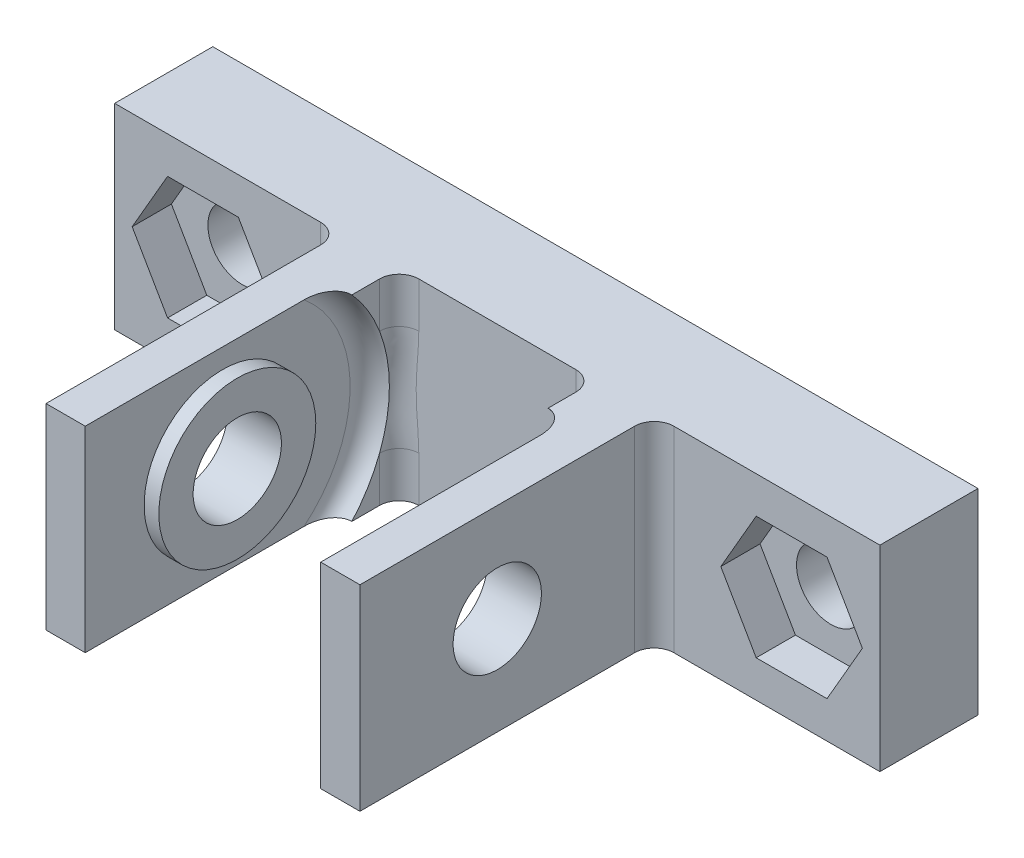
SolidWorks part; units mm, degrees
ref_plane "Front Plane" through (0, 0, 0) normal (0, 0, 1) x (1, 0, 0)
ref_plane "Top Plane" through (0, 0, 0) normal (0, 1, 0) x (1, 0, 0)
ref_plane "Right Plane" through (0, 0, 0) normal (1, 0, 0) x (0, 0, -1)
sketch "Sketch1" plane through (0, 0, 0) normal (0, 1, 0) x (1, 0, 0)
  line L0 (0, 0) -> (0, -20.0709) construction
  line L1 (-8, 0) -> (8, 0)
  line L2 (8, 0) -> (8, -20)
  line L3 (8, -20) -> (5, -20)
  line L4 (5, -20) -> (5, -5)
  line L5 (5, -5) -> (-5, -5)
  line L6 (-5, -20) -> (-5, -5)
  line L7 (-8, -20) -> (-5, -20)
  line L8 (-8, 0) -> (-8, -20)
  line L9 (5, -20) -> (5, -5)
  point P9 (0, -5)
  dimension "D1" = 5
  dimension "D2" = 3
  dimension "D3" = 15
  dimension "D4" = 5
extrude "Boss-Extrude1" add sketch "Sketch1" along normal blind 10 contours L1 L0 L5 L4 L3 L2 | L0 L1 L8 L7 L6 L5 region at (5.3235, 0, 7.7941) region at (-5.3235, 0, 7.7941)
sketch "Sketch2" plane through (8, 0, 0) normal (1, 0, 0) x (0, 0, -1)
  line L0 (-20, 5) -> (0, 5) construction
  line L1 (-20, 10) -> (-20, 0) construction
  line L2 (0, 10) -> (0, 0) construction
  circle A0 centre (-13, 5) radius 2.25
  dimension "D1" = 4.5
  dimension "D2" = 13
extrude "Cut-Extrude1" cut sketch "Sketch2" against normal through all contours A0
sketch "Sketch3" plane through (0, 10, 0) normal (0, 1, 0) x (1, 0, 0)
  line L1 (-19.5, -5) -> (19.5, -5)
  line L2 (0, 0) -> (0, -5) construction
  line L3 (-19.5, 0) -> (19.5, 0)
  line L4 (19.5, -5) -> (19.5, 0)
  line L5 (-8, 0) -> (8, 0) construction
  line L7 (-19.5, -5) -> (-19.5, 0)
  line L8 (5, -5) -> (-5, -5) construction
  dimension "D1" = 19.5
extrude "Boss-Extrude2" add sketch "Sketch3" against normal through all
sketch "Sketch4" plane through (0, 0, 5) normal (0, 0, 1) x (1, 0, 0)
  line L0 (-19.5, 5) -> (-8, 5) construction
  line L1 (-19.5, 0) -> (-19.5, 10) construction
  line L2 (-8, 10) -> (-8, 0) construction
  line L3 (-15, 0) -> (-15, 10) construction
  line L6 (0, 0) -> (0, 10) construction
  line L7 (5, 0) -> (-5, 0) construction
  line L8 (5, 10) -> (-5, 10) construction
  line L9 (15, 0) -> (15, 10) construction
  line L10 (19.5, 5) -> (8, 5) construction
  line L11 (-15, 0) -> (-15, 10) construction
  circle A0 centre (-15, 5) radius 1.75
  circle A1 centre (15, 5) radius 1.75
  dimension "D1" = 3.5
  dimension "D2" = 15
extrude "Cut-Extrude2" cut sketch "Sketch4" against normal through all
sketch "Sketch6" plane through (-5, 0, 0) normal (1, 0, 0) x (0, 0, -1)
  line L0 (-13, 12.5) -> (-20.5, 12.5)
  line L1 (-20.5, 12.5) -> (-20.5, 5)
  line L2 (-20.5, 5) -> (-20.5, -2.5)
  line L3 (-20.5, -2.5) -> (-13, -2.5)
  arc A0 (-13, -2.5) -> (-13, 12.5) centre (-13, 5) ccw
  circle A1 centre (-13, 5) radius 2.25 construction
  dimension "D1" = 15
extrude "Cut-Extrude3" cut sketch "Sketch6" against normal blind 1
sketch "Sketch5" plane through (-6, 0, 0) normal (1, 0, 0) x (0, 0, -1)
  circle A0 centre (-13, 5) radius 4
  circle A1 centre (-13, 5) radius 2.25
  circle A2 centre (-13, 5) radius 2.25 construction
  dimension "D1" = 8
extrude "Boss-Extrude3" add sketch "Sketch5" along normal blind 0.75
mirror "Mirror1" about plane through (0, 0, 0) normal (1, 0, 0) of "Boss-Extrude3", "Cut-Extrude3"
fillet "Fillet1" radius 1 6 edges at (-6, 5, 5.5) (6, 5, 5.5) (5, 5, 5) (-5, 5, 5) (8, 5, 5) (-8, 5, 5)
sketch "Sketch7" plane through (0, 0, 5) normal (0, 0, 1) x (1, 0, 0)
  line L0 (0, 10) -> (0, 0) construction
  line L1 (16.8042, 8.125) -> (13.1958, 8.125)
  line L2 (13.1958, 8.125) -> (11.3916, 5)
  line L3 (11.3916, 5) -> (13.1958, 1.875)
  line L4 (13.1958, 1.875) -> (16.8042, 1.875)
  line L5 (16.8042, 1.875) -> (18.6084, 5)
  line L6 (18.6084, 5) -> (16.8042, 8.125)
  line L7 (4, 10) -> (-4, 10) construction
  line L8 (-18.6084, 5) -> (-16.8042, 8.125)
  line L9 (-16.8042, 1.875) -> (-18.6084, 5)
  line L10 (-13.1958, 1.875) -> (-16.8042, 1.875)
  line L11 (-11.3916, 5) -> (-13.1958, 1.875)
  line L12 (-13.1958, 8.125) -> (-11.3916, 5)
  line L13 (-16.8042, 8.125) -> (-13.1958, 8.125)
  line L14 (18.6084, 5) -> (16.8042, 8.125)
  circle A0 centre (15, 5) radius 3.125 construction
  circle A1 centre (-15, 5) radius 3.125 construction
  circle M5 centre (15, 5) radius 1.75
  dimension "D1" = 6.25
extrude "Cut-Extrude4" cut sketch "Sketch7" against normal blind 2 contours L13 L8 L9 L10 L11 L12 | L5 L6 L1 L2 L3 L4 M5 | M5 region at (17.6236, 6.5148, 5) region at (-15, 5, 5) region at (15, 5, 5)
equation "\"X-ROD-SPACING\"=45"
equation "\"Y-ROD-SPACING\"=75"
equation "\"Z-ROD-SPACING\"=17.5"
equation "\"Y-BED-OFFSET\"=2"
equation "\"Y-BED-ROD-INSET\"=3.5"
equation "\"Y-BED-SCREW-SPACING\"=209"
equation "\"Y-BED-SCREW-CUTOUT-SLOT-HEIGHT\"=2"
equation "\"T-SLOT-NUT-FILLET-RADIUS\"=0.5"
equation "\"T-SLOT-SCREW-SHAFT-RADIUS\"=1.55"
equation "\"T-SLOT-SCREW-SHAFT-CUTOUT-LENGTH\"=11"
equation "\"T-SLOT-NUT-DEPTH\"=3.5"
equation "\"T-SLOT-NUT-WIDTH\"=2.85"
equation "\"T-SLOT-NUT-END-DISTANCE\"=8"
equation "\"ACRYLIC-THICKNESS\"=10"
equation "\"ACRYLIC-THICKNESS2\"=4.5"
equation "\"ACRYLIC-TAB-CUTOUT-SIZE\"=\"ACRYLIC-THICKNESS\"+\"ACRYLIC-TAB-TOLERANCE\"*2"
equation "\"ACRYLIC-TAB-TOLERANCE\"=-.05"
equation "\"KERF\"=0.075"
equation "\"ACRYLIC-THICKNESS-TAB-CUTOUT-WIDTH\"=\"ACRYLIC-THICKNESS\"-\"KERF\"*2"
equation "\"ACRYLIC-THICKNESS-TAB-CUTOUT-HEIGHT\"=\"ACRYLIC-TAB-WIDTH\"-\"KERF\"*4"
equation "\"ACRYLIC-THICKNESS2-TAB-CUTOUT-WIDTH\"=\"ACRYLIC-THICKNESS2\"-\"KERF\"*2"
equation "\"ACRYLIC-THICKNESS2-TAB-CUTOUT-HEIGHT\"=\"ACRYLIC-TAB-WIDTH\"-\"KERF\"*4"
equation "\"ACRYLIC-TAB-WIDTH\"=\"ACRYLIC-THICKNESS\""
equation "\"ACRYLIC-M3-HOLE\"=2.9"
equation "\"SMOOTHROD-CAP-SCREW-DISTANCE\"=20"
equation "\"FRAME-WIDTH-INNER\"=370"
equation "\"NEMA17-HOLE-SPACING\"=31"
equation "\"NEMA17-CENTRAL-CUTOUT\"=22.5"
equation "\"Z-BRACKET-REACH\"=55"
equation "\"Z-ROD-INSET\"=13.5"
equation "\"TOP-BRACKET-SPACING\"=40"
equation "\"SMOOTHROD-X-LENGTH\"=350"
equation "\"SMOOTHROD-Y-LENGTH\"=350"
equation "\"SMOOTHROD-Z-LENGTH\"=350"
equation "\"SMOOTHROD-TIGHTENING-HEADROOM\"=.25"
equation "\"LEADSCREW-Z-LENGTH\"=300"
equation "\"SCREW-LENGTH-FRAME\"=\"ACRYLIC-THICKNESS\" + 10"
equation "\"SCREW-LENGTH-MOTOR\"=\"ACRYLIC-THICKNESS\" + 5"
equation "\"SCREW-LENGTH-EXTRUDER\"=28"
equation "\"SCREW-HEAD-RADIUS\"=6"
equation "\"PRINTED-M3-HOLE\"=3.5"
equation "\"PRINTED-X-SMOOTHROD-DIAMETER\"=8.8"
equation "\"PRINTED-X-SMOOTHROD-CUTOUT\"=10"
equation "\"PRINTED-X-BASE-HEIGHT\"=10"
equation "\"PRINTED-LM8UU-CUTOUT-SIZE\"=15.5"
equation "\"PRINTED-LM8UU-CUTOUT-LENGTH\"=24.5"
equation "\"PRINTED-X-IDLER-HEIGHT\"=16"
equation "\"PRINTED-M3-NUT-AF\"=6.25"
equation "\"PSU-MOUNTING-WIDTH\"=95"
equation "\"PSU-MOUNTING-HEIGHT\"=177"
equation "\"Y-BELT-TO-ROD-DISTANCE\"=20"
equation "\"SPOOL-HOLDER-ROD-SPACING\"=150"
equation "\"ACRYLIC-X-CARRIAGE-WIDTH\"=55"
equation "\"ACRYLIC-X-CARRIAGE-HEIGHT\"=75"
equation "\"ACRYLIC-X-CARRIAGE-LM8UU-CUTOUT-WIDTH\"=24.25"
equation "\"ACRYLIC-X-CARRIAGE-LM8UU-CUTOUT-HEIGHT\"=11.0"
equation "\"ACRYLIC-X-CARRIAGE-SCREW-SPACING-X\"=15"
equation "\"ACRYLIC-X-CARRIAGE-SCREW-SPACING-Y\"=33"
equation "\"ACRYLIC-X-CARRIAGE-CENTER-TAB-SPACING\"=14"
equation "\"ACRYLIC-X-CARRIAGE-EXTRUDER-OFFSET\"=26"
equation "\"ACRYLIC-X-CARRIAGE-EXTRUDER-ANGLE\"=90"
equation "\"ACRYLIC-X-CARRIAGE-EXTRUDER-SHELF-DEPTH\"=\"ACRYLIC-X-CARRIAGE-EXTRUDER-OFFSET\" + 28"
equation "\"ACRYLIC-X-CARRIAGE-EXTRUDER-BRACE-SPACING\"=23"
equation "\"ACRYLIC-X-CARRIAGE-EXTRUDER-BRACE-TAB-OFFSET\"=20"
equation "\"ACRYLIC-X-CARRIAGE-EXTRUDER-BRACE-HEIGHT\"=35"
equation "\"ACRYLIC-X-CARRIAGE-EXTRUDER-BRACE-SCREW-SPACING\"=22"
equation "\"ACRYLIC-X-CARRIAGE-DUAL-WIDTH-MULTIPLIER\"=1.65"
equation "\"ACRYLIC-X-CARRIAGE-DUAL-HOTEND-SPACING\"=42"
equation "\"ACRYLIC-X-CARRIAGE-DUAL-WIDTH\"=75"
equation "\"ACRYLIC-X-CARRIAGE-DUAL-FAN-OFFSET\"=52"
equation "\"ACRYLIC-X-CARRIAGE-DUAL-FAN-HEIGHT\"=20"
equation "\"ACRYLIC-X-CARRIAGE-DUAL-HOTEND-SEPARATION\"=36"
equation "\"ACRYLIC-X-CARRIAGE-DUAL-MOUNT-PLATE-DEPTH\"=75"
equation "\"ACRYLIC-X-CARRIAGE-DUAL-MOUNT-BRACE-WIDTH\"=33"
equation "\"ACRYLIC-X-CARRIAGE-DUAL-MOUNT-SCREW-WIDTH\"=40"
equation "\"BLOWER-FAN-WIDTH\"=15"
equation "\"D1@Sketch7\"=\"PRINTED-M3-NUT-AF\""
